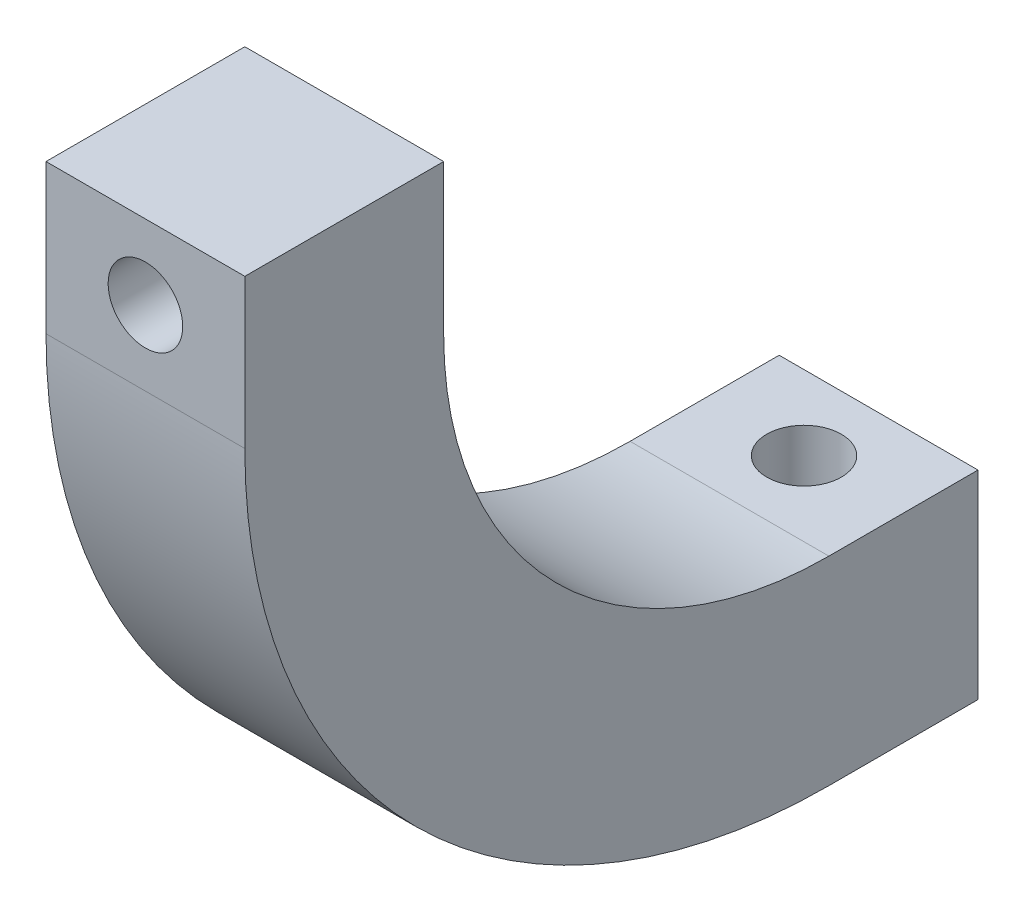
SolidWorks part; units mm, degrees
ref_plane "Front Plane" through (0, 0, 0) normal (0, 0, 1) x (1, 0, 0)
ref_plane "Top Plane" through (0, 0, 0) normal (0, 1, 0) x (1, 0, 0)
ref_plane "Right Plane" through (0, 0, 0) normal (1, 0, 0) x (0, 0, -1)
ref_axis "Z" through (0, 0, 22.75) along (0, 0, -1)
sketch "Sketch4" plane through (0, 0, 0) normal (0, 0, 1) x (1, 0, 0)
  circle A0 centre (0, 0) radius 17.5 construction
  dimension "D1" = 35
sketch "Sketch5" plane through (0, 0, 0) normal (1, 0, 0) x (0, 0, -1)
  line L0 (-18.5, 3) -> (-18.5, 0)
  line L1 (-18.5, 0) -> (-18.5, -3)
  line L2 (-26.5, -3) -> (-26.5, 3)
  line L6 (-26.5, 3) -> (-18.5, 3)
  line L12 (-22.75, 0) -> (-13.0351, 0) construction
  line L13 (0, 0) -> (-14.9091, -14.9091) construction
  line L14 (0, 0) -> (7.0065, 0) construction
  line L15 (0, -18.5) -> (-3, -18.5)
  line L16 (3, -18.5) -> (0, -18.5)
  line L17 (-3, -26.5) -> (3, -26.5)
  line L18 (3, -26.5) -> (3, -18.5)
  circle A0 centre (0, 0) radius 14 construction
  arc A1 (-18.5, -3) -> (-3, -18.5) centre (-3, -3) ccw
  arc A2 (-26.5, -3) -> (-3, -26.5) centre (-3, -3) ccw
  point P2 (9.4307, -21)
  point P4 (0, -2.1363)
  point P20 (-20.5214, -4.6985)
  point P22 (-36.7289, 3)
  dimension "D1" = 28
  dimension "D4" = 3
  dimension "D2" = 45
  dimension "D3" = 8
  dimension "D5" = 18.5
sketch "Sketch6" plane through (0, 0, 0) normal (0, 1, 0) x (1, 0, 0)
  circle A0 centre (0, 0) radius 17.5 construction
  dimension "D1" = 35
extrude "Boss-Extrude1" add sketch "Sketch5" along normal blind 4 and the other way blind 4
sketch "Sketch7" plane through (0, 0, 0) normal (0, 0, 1) x (1, 0, 0)
  circle A0 centre (0, 0) radius 1.5
  dimension "D1" = 3
extrude "Cut-Extrude1" cut sketch "Sketch7" along normal through all
sketch "Sketch8" plane through (0, 0, 0) normal (0, 1, 0) x (1, 0, 0)
  circle A0 centre (0, 0) radius 1.5
  dimension "D1" = 3
extrude "Cut-Extrude2" cut sketch "Sketch8" against normal through all
ref_axis "Y" through (0, -9.3489, 0) along (0, -1, 0)
equation "\"rbracket-width\"= \"L2Thickness\""
equation "\"EyeCaptureRadius\"= ( \"EyeDiameter\" + \"EyeClearance\" ) / 2"
equation "\"rbracket_planetocenterline_dist\"= \"BasePlaneDistance\""
equation "\"EyeDiameter\" = 35"
equation "\"BasePlaneDistance\" = 30"
equation "\"EyeClearance\" = 2"
equation "\"D1@Sketch4\"=\"EyeDiameter\""
equation "\"D1@Sketch6\"=\"EyeDiameter\""
equation "\"D1@Boss-Extrude1\"=\"rbracket-width\"/2"
equation "\"D2@Boss-Extrude1\"=\"rbracket-width\"/2"
equation "\"L2Thickness\" = 8"
equation "\"D3@Sketch5\"=\"L2Thickness\""
equation "\"D5@Sketch5\"=(\"EyeDiameter\"+\"EyeClearance\")/2"
